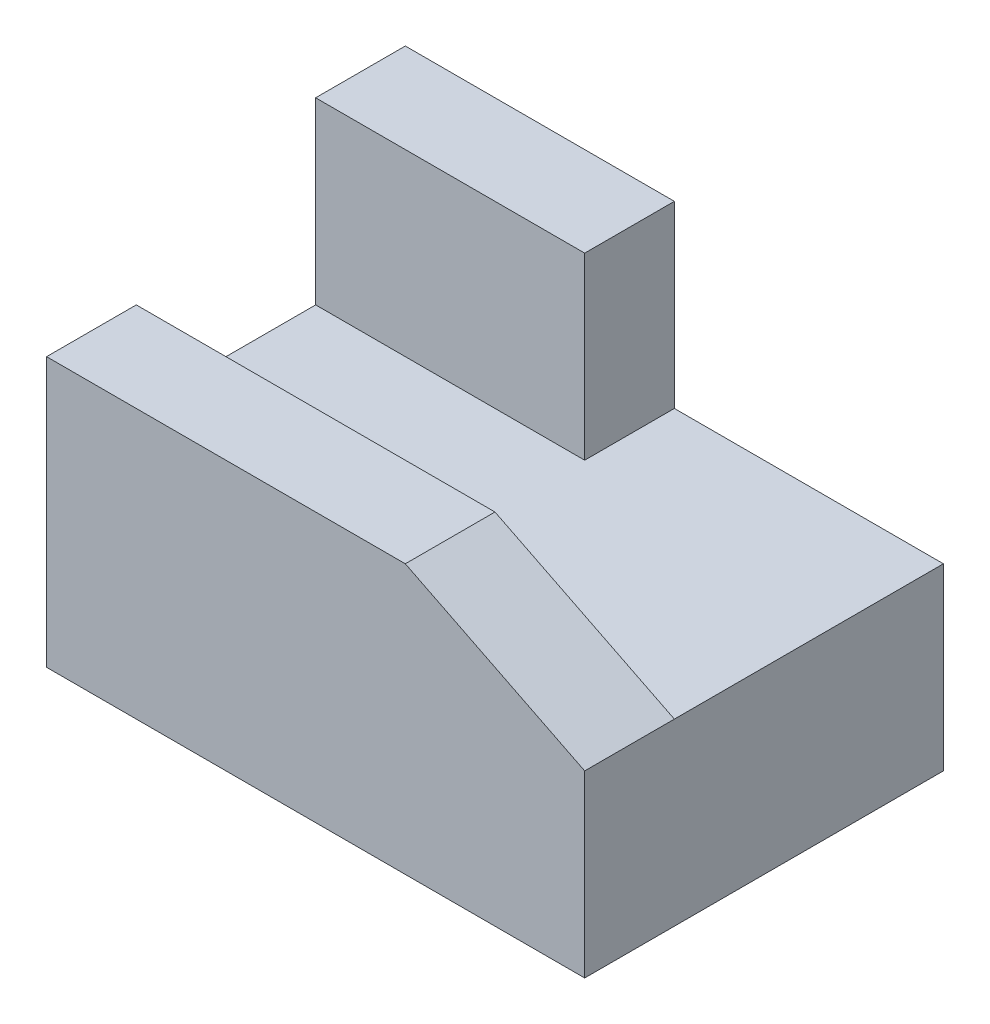
SolidWorks part; units mm, degrees
ref_plane "前基準面" through (0, 0, 0) normal (0, 0, 1) x (1, 0, 0)
ref_plane "上基準面" through (0, 0, 0) normal (0, 1, 0) x (1, 0, 0)
ref_plane "右基準面" through (0, 0, 0) normal (1, 0, 0) x (0, 0, -1)
sketch "草圖1" plane through (0, 0, 0) normal (0, 1, 0) x (1, 0, 0)
  line L1 (15, 10) -> (-15, 10)
  line L2 (15, 10) -> (15, -10)
  line L3 (15, -10) -> (-15, -10)
  line L4 (-15, 10) -> (-15, -10)
  line L5 (15, 10) -> (-15, -10) construction
  line L6 (15, -10) -> (-15, 10) construction
  line L7 (-15, 10) -> (0, 10)
  line L8 (-15, 10) -> (-15, 5)
  line L9 (-15, 5) -> (0, 5)
  line L10 (0, 10) -> (0, 5)
  line L11 (-15, -10) -> (15, -10)
  line L12 (-15, -10) -> (-15, -5)
  line L13 (-15, -5) -> (15, -5)
  line L14 (15, -10) -> (15, -5)
  line L15 (15, -5) -> (5, -5)
  line L16 (15, -5) -> (15, -10)
  line L17 (15, -10) -> (5, -10)
  line L18 (5, -5) -> (5, -10)
  point P0 (0, 0)
  dimension "D1" = 20
  dimension "D2" = 30
  dimension "D3" = 5
  dimension "D4" = 15
  dimension "D5" = 5
  dimension "D6" = 10
extrude "填料-伸長1" add sketch "草圖1" along normal blind 10 contours L10 L1 L4 L9 | L4 L13 L2 L1 L10 L9 | L18 L13 L4 L11 | L13 L18 L3 L2 region at (1.5, 0, -1.5) region at (-7.5, 0, -7.5) region at (10, 0, 7.5) region at (-5, 0, 7.5)
extrude "填料-伸長2" add sketch "草圖1<3>" along normal blind 15 contours L18 L13 L4 L11 | L13 L18 L3 L2 region at (10, 0, 7.5) region at (-5, 0, 7.5)
sketch "草圖1<3>" plane through (0, 0, 0) normal (0, 1, 0) x (1, 0, 0) same geometry as "草圖1"
extrude "填料-伸長3" add sketch "草圖1<4>" along normal blind 20 contours L10 L1 L4 L9 region at (-7.5, 0, -7.5)
sketch "草圖1<4>" plane through (0, 0, 0) normal (0, 1, 0) x (1, 0, 0) same geometry as "草圖1"
sketch "草圖2" plane through (0, 0, 10) normal (0, 0, 1) x (1, 0, 0)
  line L0 (5, 15) -> (15, 10)
  line L1 (15, 15) -> (-15, 15) construction
  line L2 (15, 10) -> (15, 15)
  line L3 (15, 15) -> (5, 15)
  dimension "D1" = 10
extrude "除料-伸長1" cut sketch "草圖2" against normal blind 20
scale "縮放比例1" scale about centroid uniform scaling yes scale factor 0.2
